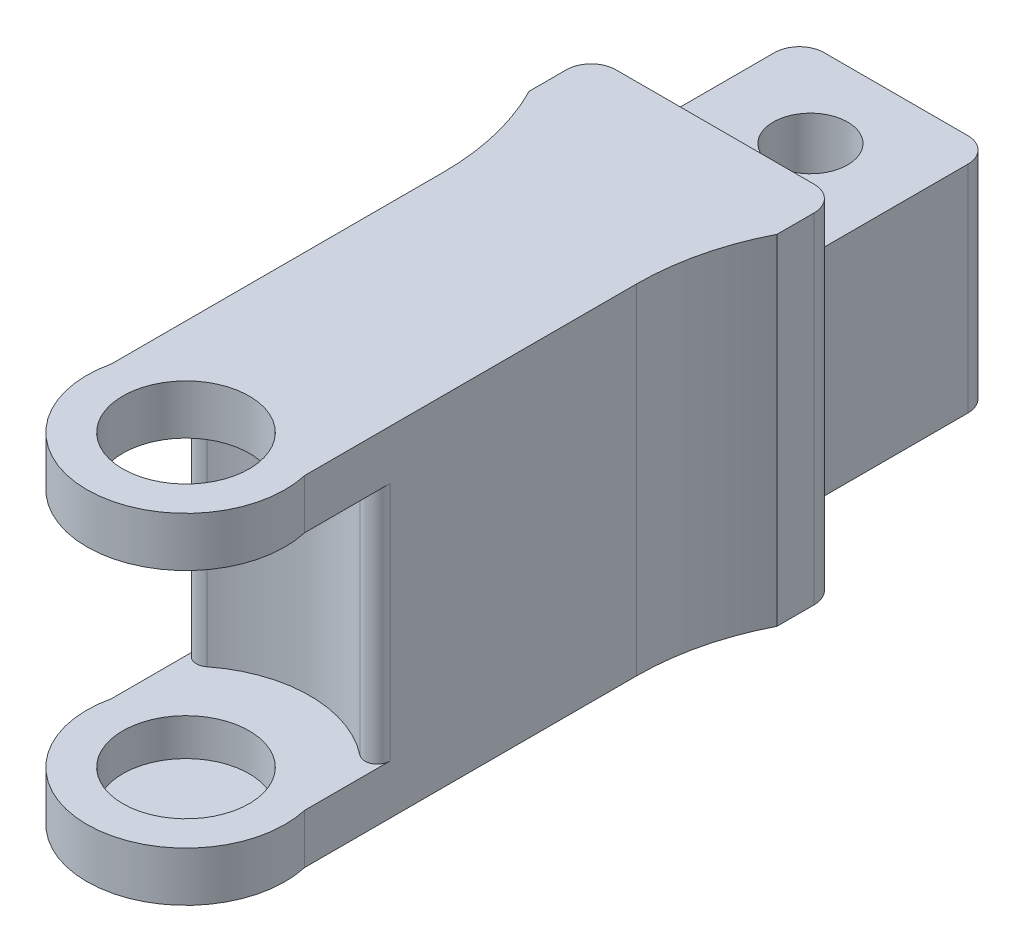
SolidWorks part; units mm, degrees
ref_plane "Front Plane" through (0, 0, 0) normal (0, 0, 1) x (1, 0, 0)
ref_plane "Top Plane" through (0, 0, 0) normal (0, 1, 0) x (1, 0, 0)
ref_plane "Right Plane" through (0, 0, 0) normal (1, 0, 0) x (0, 0, -1)
sketch "Sketch2" plane through (0, 0, 0) normal (0, 1, 0) x (1, 0, 0)
  line L0 (-3.9, -3.65) -> (-3.9, -21.8711)
  line L1 (-3.9, 3.65) -> (3.9, 3.65)
  line L2 (-3.9, 3.65) -> (-3.9, -3.65)
  line L3 (-3.9, -3.65) -> (3.9, -3.65)
  line L4 (3.9, 3.65) -> (3.9, -3.65)
  line L5 (-3.9, 3.65) -> (3.9, -3.65) construction
  line L6 (-3.9, -3.65) -> (3.9, 3.65) construction
  line L7 (3.9, -3.65) -> (3.9, -21.8711)
  line L9 (-5, -6.15) -> (5, -6.15)
  line L10 (-5, -6.15) -> (-5, -3.65)
  line L11 (-5, -3.65) -> (5, -3.65)
  line L12 (5, -6.15) -> (5, -3.65)
  line L13 (-5, -6.15) -> (5, -3.65) construction
  line L14 (-5, -3.65) -> (5, -6.15) construction
  circle A1 centre (0, -25) radius 2.55
  circle A2 centre (0, -25) radius 5
  circle A3 centre (0, 0.2) radius 1.5
  point P10 (0, -4.9)
  dimension "D1" = 25
  dimension "D4" = 5.1
  dimension "D5" = 10
  dimension "D8" = 3
  dimension "D2" = 7.3
  dimension "D3" = 7.8
  dimension "D6" = 2.5
  dimension "D7" = 10
  dimension "D9" = 3.85
extrude "Boss-Extrude1" add sketch "Sketch2" along normal blind 8.7 contours L4 L1 L2 L3 A3 | A2 L7 L3 L0 | L0 L9 L7 L3 | L11 L10 L9 L0 | L9 L12 L11 L7 region at (0, 0, 4.9) region at (-3.7932, 0, 0) region at (-4.45, 0, 4.9) region at (0, 0, 13.369) region at (4.45, 0, 4.9)
sketch "Sketch3" plane through (0, 8.7, 0) normal (0, 1, 0) x (1, 0, 0)
  line L0 (-5, -6.15) -> (5, -6.15) construction
  line L1 (5, -6.15) -> (5, -3.65) construction
  line L2 (-5, -3.65) -> (5, -3.65) construction
  line L3 (-5, -6.15) -> (-5, -3.65) construction
  line L4 (-5, -6.15) -> (5, -6.15)
  line L5 (5, -6.15) -> (5, -3.65)
  line L6 (-5, -3.65) -> (5, -3.65)
  line L7 (-5, -6.15) -> (-5, -3.65)
  line L8 (-3.9, -6.15) -> (-3.9, -24.1112)
  line L9 (3.9, -6.15) -> (3.9, -24.1112)
  circle A0 centre (0, -25) radius 2.55 construction
  circle A1 centre (0, -25) radius 2.55
  circle A2 centre (0, -25) radius 4
  line M5 (-3.9, -3.65) -> (-5, -3.65)
  line M6 (-5, -3.65) -> (-5, -6.15)
  line M7 (-5, -6.15) -> (-3.9, -6.15)
  line M8 (-3.9, -6.15) -> (-3.9, -21.8711)
  arc M9 (-3.9, -21.8711) -> (3.9, -21.8711) centre (0, -25) cw
  line M10 (3.9, -21.8711) -> (3.9, -6.15)
  line M11 (3.9, -6.15) -> (5, -6.15)
  line M12 (5, -6.15) -> (5, -3.65)
  line M13 (5, -3.65) -> (3.9, -3.65)
  dimension "D1" = 8
extrude "Boss-Extrude2" add sketch "Sketch3" along normal blind 2.5 contours L6 L4 M5 M6 M7 M11 M12 M13 | L4 M8 M9 M10 | A2 A1 | A2 L9 L8 M9 region at (0, 8.7, 4.9) region at (0, 8.7, 13.369) region at (0, 8.7, 20.0882) region at (0, 8.7, 21.1131)
extrude "Boss-Extrude3" add sketch "Sketch3<3>" against normal blind 2.5 from surface contours A2 A1 | A2 L9 L8 M9 | L4 M8 M9 M10 | L6 L4 M5 M6 M7 M11 M12 M13 region at (0, 8.7, 4.9) region at (0, 8.7, 13.369) region at (0, 8.7, 20.0882) region at (0, 8.7, 21.1131) starting at face at (0, 0, 1.3)
sketch "Sketch3<3>" plane through (0, 8.7, 0) normal (0, 1, 0) x (1, 0, 0) same geometry as "Sketch3"
extrude "Cut-Extrude1" cut sketch "Sketch2<3>" along normal offset from surface (9.7 mm away) 0.5 from offset 0.5 contours A2 A1 region at (0, 0, 20.1414) up to face at (0, 8.7, 23.7456) offset beyond the face yes offset against normal yes
sketch "Sketch2<3>" plane through (0, 0, 0) normal (0, 1, 0) x (1, 0, 0) same geometry as "Sketch2"
extrude "Boss-Extrude4" add sketch "Sketch2<4>" along normal blind 0.5 from surface contours A1 region at (0, 0, 25) starting at face at (0, -2.5, 27.55)
sketch "Sketch2<4>" plane through (0, 0, 0) normal (0, 1, 0) x (1, 0, 0) same geometry as "Sketch2"
fillet "Fillet1" radius 10 2 edges at (-3.9, 4.35, 6.15) (3.9, 4.35, 6.15)
fillet "Fillet2" radius 0.5 2 edges at (3.9, 4.35, 21.8711) (-3.9, 4.35, 21.8711)
fillet "Fillet3" radius 1 4 edges at (3.9, 4.35, -3.65) (-3.9, 4.35, -3.65) (-5, 4.35, 3.65) (5, 4.35, 3.65)
